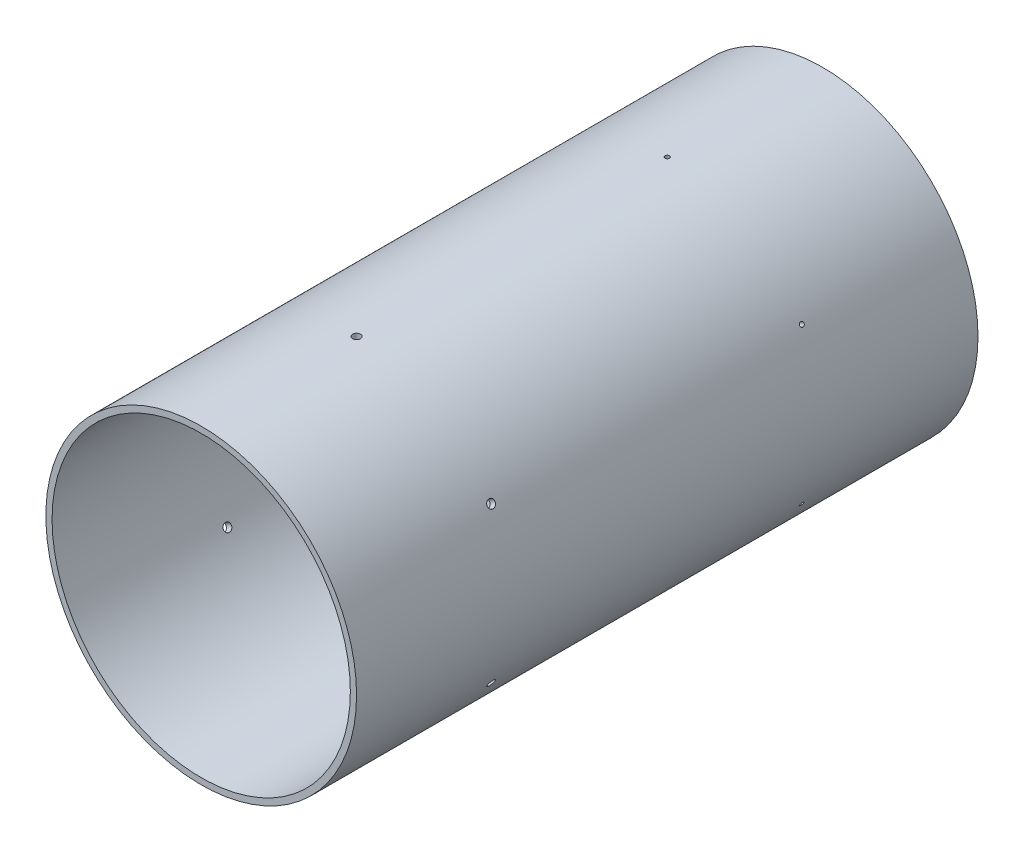
SolidWorks part; units mm, degrees
ref_plane "Front Plane" through (0, 0, 0) normal (0, 0, 1) x (1, 0, 0)
ref_plane "Top Plane" through (0, 0, 0) normal (0, 1, 0) x (1, 0, 0)
ref_plane "Right Plane" through (0, 0, 0) normal (1, 0, 0) x (0, 0, -1)
sketch "Sketch1" plane through (0, 0, 0) normal (0, 0, 1) x (1, 0, 0)
  circle A0 centre (0, 0) radius 79.375
  circle A1 centre (0, 0) radius 76.2
  dimension "D1" = 158.75
  dimension "D2" = 3.175
extrude "Boss-Extrude1" add sketch "Sketch1" along normal blind 317.5
ref_plane "Plane1" through (0, 79.375, 0) normal (0, 1, 0) x (1, 0, 0)
sketch "Sketch2" plane through (0, 79.375, 0) normal (0, 1, 0) x (1, 0, 0)
  line L0 (79.375, 0) -> (-79.375, 0) construction
  point P0 (0, -79.375)
  dimension "D1" = 79.375
hole_wizard "#4-40 Tapped Hole1" positions "Sketch5" profile "Sketch6" tap size "#4-40" standard "ANSI Inch" end condition up to next
sketch "Sketch5" plane through (0, 79.375, 0) normal (0, 1, 0) x (1, 0, 0)
  point P0 (0, -79.375)
sketch "Sketch6" plane through (0, 79.375, 79.375) normal (1, 0, 0) x (0, 0, 1)
  line L0 (0, 0) -> (0, 3.175)
  line L1 (0, 3.175) -> (1.1303, 3.175)
  line L2 (1.1303, 3.175) -> (1.1303, 0)
  line L5 (1.1303, 0) -> (0, 0)
  line L11 (0, -6.35) -> (0, 107.95) construction
  dimension "Thru Tap Drill Dia." = 2.2606
  dimension "Thru Tap Drill Depth" = 3.175
cosmetic thread "Hole Thread1"
sketch "Sketch7" plane through (0, 79.375, 0) normal (0, 1, 0) x (1, 0, 0)
  line L0 (-79.375, -317.5) -> (79.375, -317.5) construction
  point P0 (0, -238.125)
  dimension "D1" = 79.375
hole_wizard "#10-32 Tapped Hole1" positions "Sketch8" profile "Sketch9" tap size "#10-32" standard "ANSI Inch" end condition up to next
sketch "Sketch8" plane through (0, 79.375, 0) normal (0, 1, 0) x (1, 0, 0)
  point P0 (0, -238.125)
sketch "Sketch9" plane through (0, 79.375, 238.125) normal (1, 0, 0) x (0, 0, 1)
  line L0 (0, 0) -> (0, 3.175)
  line L1 (0, 3.175) -> (2.0193, 3.175)
  line L2 (2.0193, 3.175) -> (2.0193, 0)
  line L5 (2.0193, 0) -> (0, 0)
  line L11 (0, -6.35) -> (0, 107.95) construction
  dimension "Thru Tap Drill Dia." = 4.0386
  dimension "Thru Tap Drill Depth" = 3.175
cosmetic thread "Hole Thread2"
pattern_circular "CirPattern1" count 6 over 360 about axis through (0, 0, 317.5) along (0, 0, 1) of "#4-40 Tapped Hole1", "#10-32 Tapped Hole1"
cosmetic thread "Hole Thread3"
cosmetic thread "Hole Thread4"
cosmetic thread "Hole Thread5"
cosmetic thread "Hole Thread6"
cosmetic thread "Hole Thread7"
cosmetic thread "Hole Thread8"
cosmetic thread "Hole Thread9"
cosmetic thread "Hole Thread10"
cosmetic thread "Hole Thread11"
cosmetic thread "Hole Thread12"
